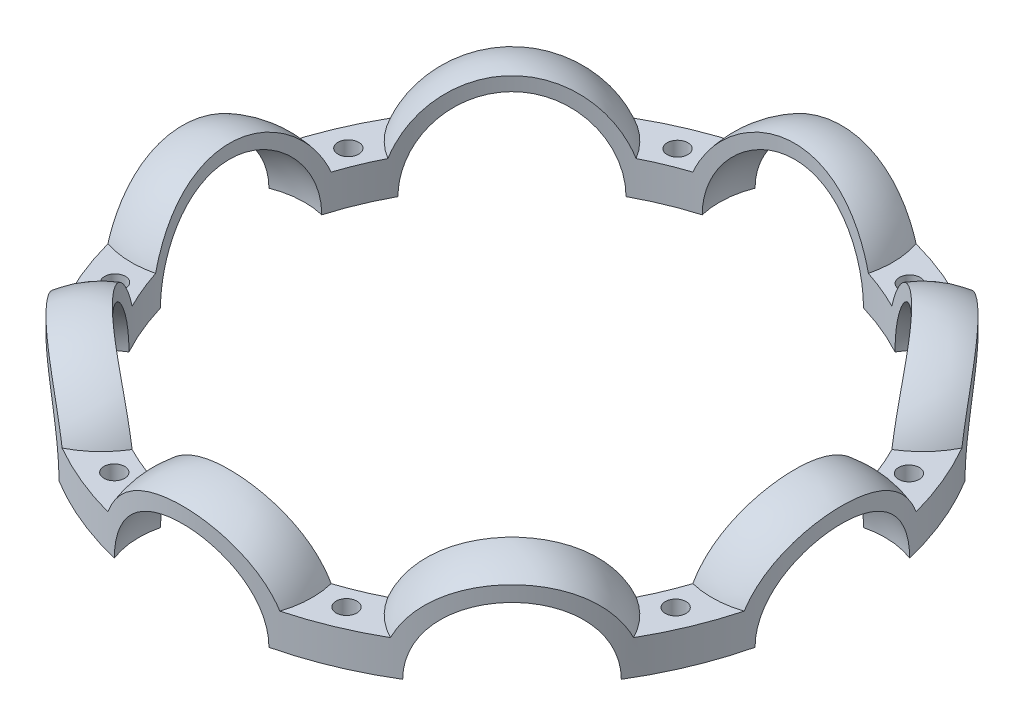
SolidWorks part; units mm, degrees
ref_plane "Front Plane" through (0, 0, 0) normal (0, 0, 1) x (1, 0, 0)
ref_plane "Top Plane" through (0, 0, 0) normal (0, 1, 0) x (1, 0, 0)
ref_plane "Right Plane" through (0, 0, 0) normal (1, 0, 0) x (0, 0, -1)
sketch "Sketch1" plane through (0, 0, 0) normal (0, 1, 0) x (1, 0, 0)
  line L0 (0, 0) -> (55.9342, 0) construction
  line L1 (14, 0) -> (15, 0)
  line L2 (28, 0) -> (27, 0)
  arc A0 (15, 0) -> (27, 0) centre (21, 0) ccw
  arc A1 (14, 0) -> (28, 0) centre (21, 0) ccw
  dimension "D1" = 14
  dimension "D2" = 12
  dimension "D3" = 21
revolve "Revolve1" add sketch "Sketch1" angle 180 about L2
sketch "Sketch2" plane through (0, 0, 0) normal (0, 0, 1) x (1, 0, 0)
  line L0 (0, -13.3572) -> (0, 21.1889) construction
pattern_circular "CirPattern1" count 8 over 360 about axis through (0, -13.3572, 0) along (0, 1, 0) reverse direction yes of bodies 101
sketch "Sketch3" plane through (0, 0, 0) normal (0, 1, 0) x (1, 0, 0)
  circle A0 centre (0, 0) radius 26
  circle A1 centre (0, 0) radius 16
  dimension "D1" = 52
  dimension "D2" = 32
extrude "Cut-Extrude3" cut sketch "Sketch3" against normal blind 35 and the other way blind 46 flip side to cut
sketch "Sketch4" plane through (0, 0, 0) normal (0, 1, 0) x (1, 0, 0)
  circle A0 centre (0, 0) radius 26
  circle A1 centre (0, 0) radius 16
  dimension "D1" = 32
extrude "Boss-Extrude1" add sketch "Sketch4" along normal blind 2.5
sketch "Sketch5" plane through (0, 0, 0) normal (0, 1, 0) x (1, 0, 0)
  line L0 (0, 0) -> (30.7519, 0) construction
  line L2 (15, 0) -> (27, 0)
  arc A2 (15, 0) -> (27, 0) centre (21, 0) ccw
  dimension "D1" = 12
revolve "Cut-Revolve1" cut sketch "Sketch5" angle 360 about L0
pattern_circular "CirPattern3" count 8 over 360 about axis through (0, 0, 0) along (0, 1, 0) of "Cut-Revolve1"
sketch "Sketch6" plane through (0, 0, 0) normal (0, 1, 0) x (1, 0, 0)
  circle A0 centre (0, 0) radius 24.6109
  circle A1 centre (0, 0) radius 18.8087
extrude "Cut-Extrude4" cut sketch "Sketch6" against normal through all both and the other way through all flip side to cut
sketch "Sketch7" plane through (0, 0, 0) normal (0, 1, 0) x (1, 0, 0)
  circle A0 centre (0, 0) radius 20.444
extrude "Cut-Extrude5" cut sketch "Sketch7" against normal through all both and the other way through all
sketch "Sketch8" plane through (0, 0, 0) normal (0, 1, 0) x (1, 0, 0)
  circle A0 centre (0, 0) radius 23.8393
extrude "Cut-Extrude6" cut sketch "Sketch8" along normal through all both and the other way through all flip side to cut
sketch "Sketch9" plane through (0, 2.5, 0) normal (0, 1, 0) x (1, 0, 0)
  circle A0 centre (-8.3716, 20.3449) radius 0.75
  arc A1 (-6.3479, 19.4335) -> (-9.2529, 18.2302) centre (0, 0) ccw construction
  dimension "D1" = 1.5
  dimension "D2" = 22
extrude "Cut-Extrude7" cut sketch "Sketch9" against normal through all both and the other way through all
pattern_circular "CirPattern4" count 8 over 360 about axis through (0, -0.3442, 0) along (0, 1, 0) of "Cut-Extrude7"
